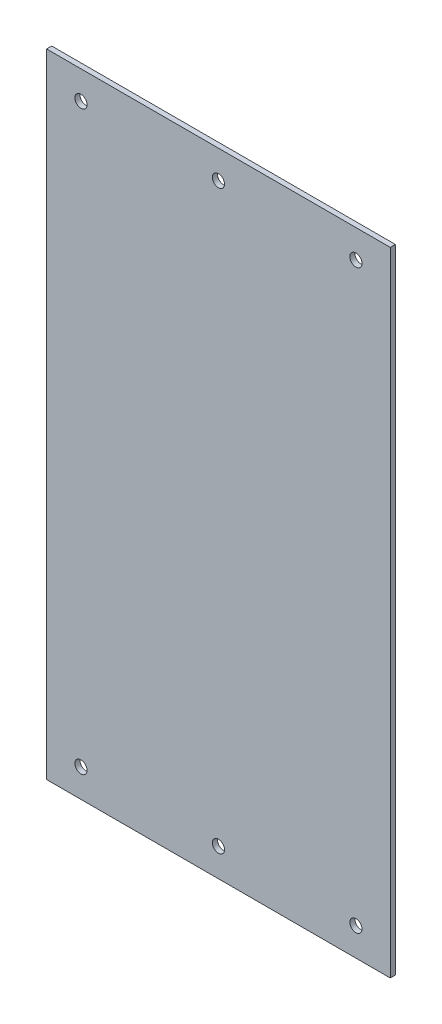
SolidWorks part; units mm, degrees
material "1060 Alloy"
ref_plane "Front Plane" through (0, 0, 0) normal (0, 0, 1) x (1, 0, 0)
ref_plane "Top Plane" through (0, 0, 0) normal (0, 1, 0) x (1, 0, 0)
ref_plane "Right Plane" through (0, 0, 0) normal (1, 0, 0) x (0, 0, -1)
sketch "Sketch1" plane through (0, 0, 0) normal (0, 0, 1) x (1, 0, 0)
  line L0 (55, 0) -> (-55, 0) construction
  line L1 (-77.5, 142.695) -> (77.5, 142.695)
  line L2 (-77.5, 142.695) -> (-77.5, -142.695)
  line L3 (-77.5, -142.695) -> (77.5, -142.695)
  line L4 (77.5, 142.695) -> (77.5, -142.695)
  line L5 (-77.5, 142.695) -> (77.5, -142.695) construction
  line L6 (-77.5, -142.695) -> (77.5, 142.695) construction
  point P0 (0, 0)
  point P5 (-62, 129.995)
  point P7 (0, 129.995)
  point P8 (62, 129.995)
  point P13 (62, -129.995)
  point P14 (0, -129.995)
  point P15 (-62, -129.995)
  dimension "D1" = 155
  dimension "D2" = 285.39
  dimension "D3" = 15.5
  dimension "D4" = 15.5
  dimension "D5" = 12.7
extrude "Boss-Extrude1" add sketch "Sketch1" along normal blind 2.305
hole_wizard "M5 Clearance Hole1" positions "Sketch2" profile "Sketch3" hole size "M5" standard "ANSI Metric" end condition through all
sketch "Sketch2" plane through (0, 0, 2.305) normal (0, 0, 1) x (1, 0, 0)
  point P0 (-62, 129.995)
  point P3 (0, 129.995)
  point P6 (62, 129.995)
  point P9 (-62, -129.995)
  point P12 (0, -129.995)
  point P15 (62, -129.995)
sketch "Sketch3" plane through (-62, 129.995, 2.305) normal (1, 0, 0) x (0, -1, 0)
  line L0 (0, 0) -> (0, 2.305)
  line L1 (0, 2.305) -> (2.75, 2.305)
  line L2 (2.75, 2.305) -> (2.75, 0)
  line L5 (2.75, 0) -> (0, 0)
  line L11 (0, -6.35) -> (0, 107.95) construction
  dimension "Thru Hole Dia." = 5.5
  dimension "Thru Hole Depth" = 2.305
